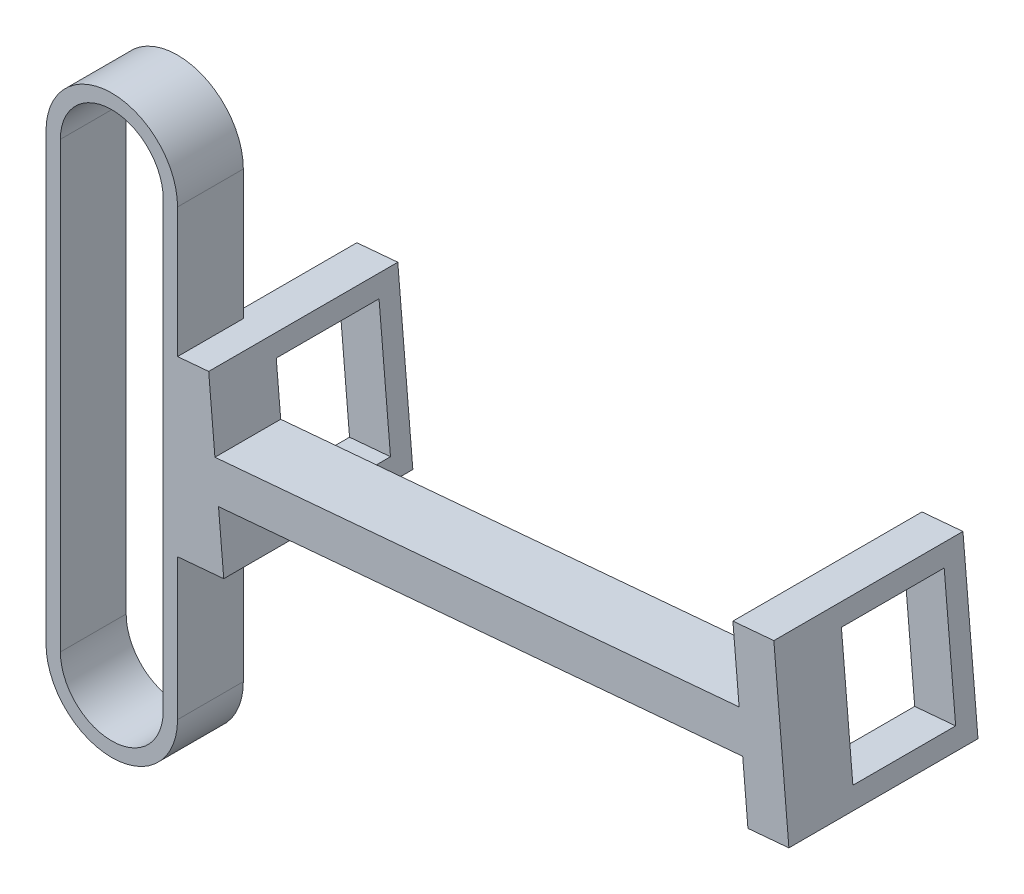
SolidWorks part; units mm, degrees
ref_plane "Front Plane" through (0, 0, 0) normal (0, 0, 1) x (1, 0, 0)
ref_plane "Top Plane" through (0, 0, 0) normal (0, 1, 0) x (1, 0, 0)
ref_plane "Right Plane" through (0, 0, 0) normal (1, 0, 0) x (0, 0, -1)
sketch "Sketch1" plane through (0, 0, 0) normal (0, 0, 1) x (1, 0, 0)
  line L1 (-10.16, -34.29) -> (10.16, -34.29)
  line L2 (-10.16, -34.29) -> (-10.16, 34.29)
  line L3 (-10.16, 34.29) -> (10.16, 34.29)
  line L4 (10.16, -34.29) -> (10.16, 34.29)
  line L5 (-10.16, -34.29) -> (10.16, 34.29) construction
  line L6 (-10.16, 34.29) -> (10.16, -34.29) construction
  circle A0 centre (0, 34.29) radius 10.16
  circle A1 centre (0, -34.29) radius 10.16
  point P0 (0, 0)
  dimension "D1" = 20.32
  dimension "D2" = 68.58
extrude "Boss-Extrude1" add sketch "Sketch1" along normal blind 10.16 contours A0 | L2 L1 L4 L3 | A1
sketch "Sketch2" plane through (0, 0, 10.16) normal (0, 0, 1) x (1, 0, 0)
  line L0 (7.9375, 0) -> (10.16, 0) construction
  line L1 (-7.9375, -34.29) -> (7.9375, -34.29)
  line L2 (-7.9375, -34.29) -> (-7.9375, 34.29)
  line L3 (-7.9375, 34.29) -> (7.9375, 34.29)
  line L4 (7.9375, -34.29) -> (7.9375, 34.29)
  line L5 (-7.9375, -34.29) -> (7.9375, 34.29) construction
  line L6 (-7.9375, 34.29) -> (7.9375, -34.29) construction
  line L7 (10.16, -34.29) -> (10.16, 34.29) construction
  line L8 (0, 42.2275) -> (0, 44.45) construction
  circle A0 centre (0, 34.29) radius 7.9375
  circle A1 centre (0, -34.29) radius 7.9375
  arc A2 (10.16, 34.29) -> (-10.16, 34.29) centre (0, 34.29) ccw construction
  point P0 (0, 0)
  dimension "D1" = 15.875
extrude "Cut-Extrude1" cut sketch "Sketch2" against normal through all contours A0 | L2 L1 L4 L3 | A1
sketch "Sketch3" plane through (0, 0, 0) normal (0, 0, -1) x (-1, 0, 0)
  line L0 (-10.16, -34.29) -> (-10.16, 34.29) construction
  line L1 (-9.6066, 3.1387) -> (-103.2289, 11.3296)
  line L2 (-9.6066, 3.1387) -> (-10.16, -3.1871)
  line L3 (-10.16, -3.1871) -> (-103.7824, 5.0038)
  line L4 (-103.2289, 11.3296) -> (-103.7824, 5.0038)
  line L5 (-103.5057, 8.1667) -> (-10.16, 0) construction
  dimension "D1" = 6.35
  dimension "D2" = 93.98
  dimension "D3" = 85
extrude "Boss-Extrude2" add sketch "Sketch3" against normal up to surface (10.16 mm away) up to face at (0, 0, 10.16)
ref_plane "Plane1" through (9.8061, 0.8579, 0) normal (-0.9962, -0.0872, 0) x (0, 0, 1)
sketch "Sketch4" plane through (-103.0822, 1291.1777, 0) normal (-0.9962, -0.0872, 0) x (0, 0, -1)
  line L1 (19.05, 1281.9136) -> (-10.16, 1281.9136)
  line L2 (19.05, 1281.9136) -> (19.05, 1308.5836)
  line L3 (19.05, 1308.5836) -> (-10.16, 1308.5836)
  line L4 (-10.16, 1281.9136) -> (-10.16, 1308.5836)
  line L5 (19.05, 1281.9136) -> (-10.16, 1308.5836) construction
  line L6 (19.05, 1308.5836) -> (-10.16, 1281.9136) construction
  line L7 (-10.16, 1292.9591) -> (-10.16, 1261.9746) construction
  line L8 (-10.16, 1328.5226) -> (-10.16, 1260.2036) construction
  point P0 (4.445, 1295.2486)
  dimension "D1" = 29.21
  dimension "D2" = 26.67
extrude "Boss-Extrude3" add sketch "Sketch4" against normal blind 6.35
sketch "Sketch5" plane through (16.1319, 1.4114, 0) normal (0.9962, 0.0872, 0) x (0, 0, 1)
  line L0 (-19.05, 13.335) -> (-19.05, -13.335) construction
  line L1 (-15.875, -10.16) -> (0, -10.16)
  line L2 (-15.875, -10.16) -> (-15.875, 10.16)
  line L3 (-15.875, 10.16) -> (0, 10.16)
  line L4 (0, -10.16) -> (0, 10.16)
  line L5 (-15.875, -10.16) -> (0, 10.16) construction
  line L6 (-15.875, 10.16) -> (0, -10.16) construction
  line L7 (0, 35.045) -> (0, 4.0605) construction
  point P0 (-7.9375, 0)
  dimension "D2" = 20.32
  dimension "D3" = 3.175
extrude "Cut-Extrude2" cut sketch "Sketch5" against normal through all contours L3 L4 L1 L2
sketch "Sketch6" plane through (103.4285, 9.0488, 0) normal (0.9962, 0.0872, 0) x (0, 0, -1)
  line L9 (-10.16, -4.0605) -> (-10.16, -13.335)
  line L10 (-10.16, -13.335) -> (19.05, -13.335)
  line L11 (19.05, -13.335) -> (19.05, 13.335)
  line L12 (19.05, 13.335) -> (-10.16, 13.335)
  line L17 (-10.16, -4.0605) -> (-10.16, -13.335)
  line L18 (-10.16, -13.335) -> (19.05, -13.335)
  line L19 (19.05, -13.335) -> (19.05, 13.335)
  line L20 (19.05, 13.335) -> (-10.16, 13.335)
  line L32 (-10.16, 2.2895) -> (0, 2.2895)
  line L33 (-10.16, 2.2895) -> (0, 2.2895)
  line L34 (-10.16, 13.335) -> (-10.16, 2.2895)
  line L35 (-10.16, 13.335) -> (-10.16, 2.2895)
  line L36 (0, -4.0605) -> (-10.16, -4.0605)
  line L37 (0, -4.0605) -> (-10.16, -4.0605)
  line L38 (15.875, -10.16) -> (0, -10.16)
  line L39 (15.875, -10.16) -> (0, -10.16)
  line L40 (0, -10.16) -> (0, -4.0605)
  line L41 (0, -10.16) -> (0, -4.0605)
  line L42 (0, 2.2895) -> (0, 10.16)
  line L43 (0, 2.2895) -> (0, 10.16)
  line L44 (0, 10.16) -> (15.875, 10.16)
  line L45 (0, 10.16) -> (15.875, 10.16)
  line L46 (15.875, 10.16) -> (15.875, -10.16)
  line L47 (15.875, 10.16) -> (15.875, -10.16)
  dimension "D1" = 0
extrude "Boss-Extrude4" add sketch "Sketch6" against normal blind 6.35
sketch "Sketch7" plane through (9.8061, 0.8579, 0) normal (-0.9962, -0.0872, 0) x (0, 0, 1)
  line L0 (0, -4.0605) -> (0, -13.335)
  line L1 (0, -33.274) -> (0, 35.045) construction
  line L2 (-19.05, -13.335) -> (10.16, -13.335) construction
  line L3 (0, -13.335) -> (10.16, -13.335)
  line L4 (10.16, -33.274) -> (10.16, 35.045) construction
  line L5 (10.16, -13.335) -> (10.16, -4.0605)
  line L6 (10.16, -4.0605) -> (0, -4.0605)
extrude "Boss-Extrude5" add sketch "Sketch7" along normal up to next
